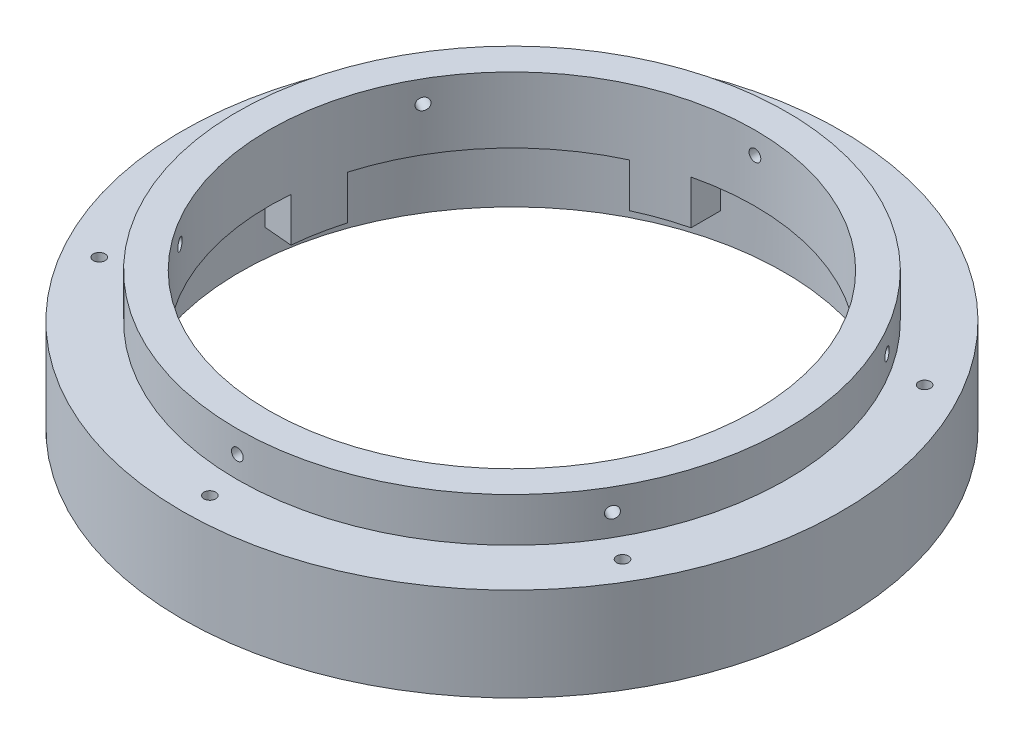
SolidWorks part; units mm, degrees
ref_plane "Front Plane" through (0, 0, 0) normal (0, 0, 1) x (1, 0, 0)
ref_plane "Top Plane" through (0, 0, 0) normal (0, 1, 0) x (1, 0, 0)
ref_plane "Right Plane" through (0, 0, 0) normal (1, 0, 0) x (0, 0, -1)
sketch "Sketch1" plane through (0, 0, 0) normal (0, 1, 0) x (1, 0, 0)
  circle A0 centre (0, 0) radius 63.5
  circle A1 centre (0, 0) radius 76.2
  circle A2 centre (0, 0) radius 56.1975
  circle A4 centre (0, 0) radius 62.865
  dimension "D1" = 152.4
  dimension "D3" = 112.395
  dimension "D2" = 12.7
  dimension "D4" = 13.335
extrude "Boss-Extrude1" add sketch "Sketch1" along normal blind 15.24 contours A0 A2 | A0 A4 region at (-63.3204, 0, 0) region at (-61.0869, 0, 0)
extrude "Boss-Extrude2" add sketch "Sketch1<4>" along normal blind 5.08 and the other way blind 16.51 contours A1 A0 | A0 A4 region at (-63.3204, 0, 0) region at (-74.0447, 0, 0)
sketch "Sketch1<4>" plane through (0, 0, 0) normal (0, 1, 0) x (1, 0, 0) same geometry as "Sketch1"
sketch "Sketch3" plane through (0, -16.51, 0) normal (0, -1, 0) x (1, 0, 0)
  line L0 (0, 0) -> (-68.319, 5.9771) construction
  line L1 (0, 0) -> (0, 69.85) construction
  line L2 (0, 0) -> (48.9804, 58.3726)
  line L3 (0, 0) -> (13.232, 75.0424)
  line L4 (-13.2113, -54.6225) -> (-13.2113, -60.147)
  line L5 (13.2113, -54.6225) -> (13.2113, -60.147)
  line L6 (-13.2113, -60.147) -> (13.2113, -60.147)
  line L7 (-13.2113, -60.147) -> (-13.2113, -61.4611)
  line L8 (-23.7501, -50.9322) -> (-26.5679, -56.975)
  line L9 (0, 0) -> (-23.7501, -50.9322) construction
  circle A0 centre (-68.319, 5.9771) radius 4.8895
  circle A1 centre (0, 69.85) radius 1.3589
  circle A2 centre (0, 0) radius 76.2 construction
  circle A5 centre (0, 0) radius 56.1975 construction
  arc A7 (-26.5679, -56.975) -> (-13.2113, -61.4611) centre (0, 0) ccw
  arc A9 (-23.7501, -50.9322) -> (-13.2113, -54.6225) centre (0, 0) ccw
  circle A12 centre (0, 0) radius 62.865 construction
  point P0 (0, -60.147)
  dimension "D4" = 9.779
  dimension "D5" = 2.7178
  dimension "D2" = 85
  dimension "D3" = 69.85
  dimension "D6" = 30
  dimension "D7" = 10
  dimension "D9" = 26.4227
  dimension "D8" = 5.5245
  dimension "D10" = 25
extrude "Cut-Extrude1" cut sketch "Sketch3" against normal blind 15.24 contours A0 region at (-68.319, -16.51, 5.9771)
extrude "Cut-Extrude2" cut sketch "Sketch3<3>" against normal through all contours A1 region at (0, -16.51, 69.85)
sketch "Sketch3<3>" plane through (0, -16.51, 0) normal (0, -1, 0) x (1, 0, 0) same geometry as "Sketch3"
pattern_circular "CirPattern1" count 3 over 360 about axis through (0, -16.51, 0) along (0, 1, 0) of "Cut-Extrude1"
pattern_circular "CirPattern2" count 6 over 360 about axis through (0, -16.51, 0) along (0, 1, 0) of "Cut-Extrude2"
ref_plane "Plane1" through (0, 0, 76.2) normal (0, 0, 1) x (1, 0, 0)
sketch "Sketch5" plane through (0, 0, 76.2) normal (0, 0, 1) x (1, 0, 0)
  line L0 (0, -16.51) -> (0, 10.16) construction
  line L1 (-1.3589, -16.51) -> (1.3589, -16.51) construction
  circle A0 centre (0, 10.16) radius 1.3589
  dimension "D2" = 2.7178
  dimension "D1" = 26.67
extrude "Cut-Extrude3" cut sketch "Sketch5" against normal up to surface (132.3811 mm away) up to face at (0, 15.24, 56.1975)
extrude "Boss-Extrude3" add sketch "Sketch3<11>" along normal blind 10.16 from surface contours L4 A9 L8 A7 L7 starting at face at (0, 0, 56.1975)
sketch "Sketch3<11>" plane through (0, -16.51, 0) normal (0, -1, 0) x (1, 0, 0) same geometry as "Sketch3"
pattern_circular "CirPattern3" count 6 over 360 about axis through (0, 15.24, 0) along (0, 1, 0) of "Cut-Extrude3", "Boss-Extrude3"
equation "\"Middle Coupler Inner Daimeter\"= 3.875in"
equation "\"Middle Coupler  Wall Thickness\" = 0.25in"
equation "\"Middle Coupler Bottom Thickness\"= 0.2in"
equation "\"Bearing Rail Offset\"= 0.45in"
equation "\"3-56 UNF Tap\"= 0.089in"
equation "\"3-48 Tap\"= 0.079in"
equation "\"3-56 UNF Clearance\"= 0.104in"
equation "\"3-48 Clearance\" = 0.104in"
equation "\"Ball Bearing Distance\"= 0.03in"
equation "\"TCA Outer Diameter\" = 6in"
equation "\"Interstage Aeroframe Wall Thickness\" = 0.072in"
equation "\"Compression Spring OD\"= 0.42in"
equation "\"10-24 Tap\"= 0.157in"
equation "\"10-24 Clearance\"= 0.196in"
equation "\"Lower Stage Fuselage Wall Thickness\" = 0.25in"
equation "\"6-32 Tap\" = 0.107in"
equation "\"6-32 Clearance\" = 0.144"
equation "\"1/4-20 Tap\" = 0.201in"
equation "\"12-24 Tap\" = 0.177in"
equation "\"D1@Sketch1\"=\"TCA Outer Diameter\""
equation "\"D5@Sketch3\"=\"6-32 Tap\""
equation "\"D1@Sketch5\"=\"D2@Boss-Extrude2\"+(\"D1@Boss-Extrude2\"+\"D1@Boss-Extrude1\")/2"
equation "\"D2@Sketch5\"=\"6-32 Tap\""
equation "\"D8@Sketch3\"=3/16+0.03"
equation "\"D3@Sketch1\"=\"Middle Coupler Inner Daimeter\" + 0.55"
equation "\"D4@Sketch3\"=0.375 + 0.01"
